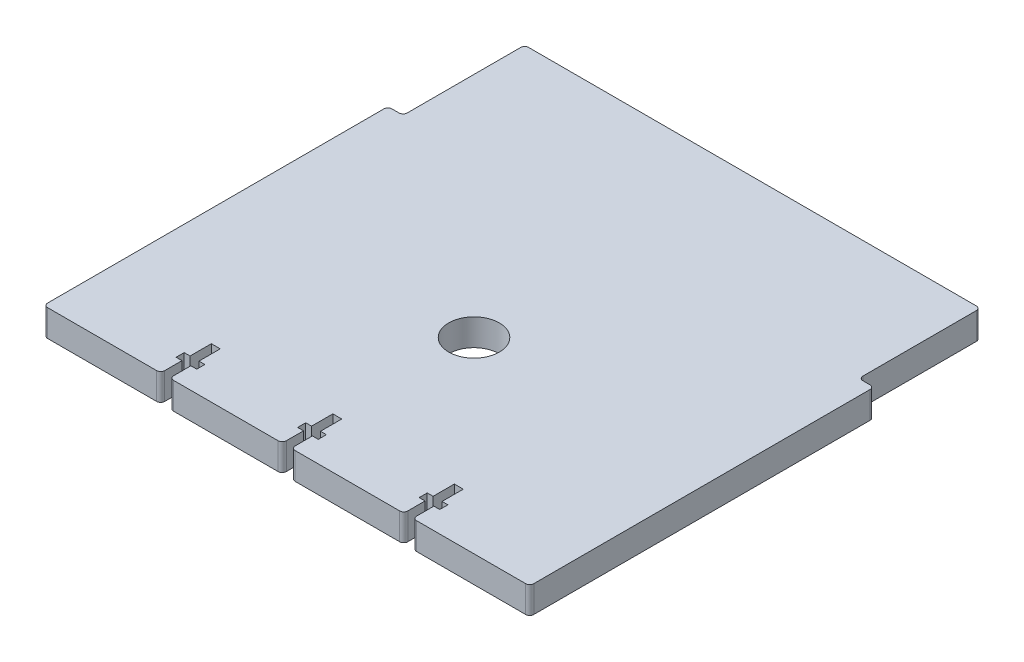
SolidWorks part; units mm, degrees
ref_plane "Front Plane" through (0, 0, 0) normal (0, 0, 1) x (1, 0, 0)
ref_plane "Top Plane" through (0, 0, 0) normal (0, 1, 0) x (1, 0, 0)
ref_plane "Right Plane" through (0, 0, 0) normal (1, 0, 0) x (0, 0, -1)
sketch "Sketch1" plane through (0, 0, 0) normal (0, 1, 0) x (1, 0, 0)
  line L1 (0, 0) -> (142.875, 0)
  line L2 (0, 107.95) -> (0, 146.05)
  line L3 (0, 146.05) -> (142.875, 146.05)
  line L4 (142.875, 107.95) -> (142.875, 146.05)
  line L5 (142.875, 0) -> (147.6375, 0)
  line L7 (142.875, 107.95) -> (147.6375, 107.95)
  line L8 (147.6375, 0) -> (147.6375, 107.95)
  line L9 (0, 0) -> (-4.7625, 0)
  line L11 (0, 107.95) -> (-4.7625, 107.95)
  line L12 (-4.7625, 0) -> (-4.7625, 107.95)
  dimension "D1" = 142.875
  dimension "D2" = 146.05
  dimension "D3" = 4.7625
  dimension "D4" = 4.7625
  dimension "D5" = 107.95
  dimension "D6" = 107.95
extrude "Boss-Extrude1" add sketch "Sketch1" along normal blind 8.382
sketch "Sketch10" plane through (0, 8.382, 0) normal (0, 1, 0) x (1, 0, 0)
  line L0 (71.4375, 146.05) -> (71.4375, 15.875) construction
  line L1 (70.0405, 9.2075) -> (68.199, 9.2075)
  line L2 (108.1405, 15.875) -> (110.9345, 15.875)
  line L3 (142.875, 146.05) -> (0, 146.05) construction
  line L4 (-4.7625, 0) -> (147.6375, 0) construction
  line L5 (70.0405, 6.6675) -> (70.0405, 0)
  line L6 (70.0405, 15.875) -> (72.8345, 15.875)
  line L7 (70.0405, 15.875) -> (70.0405, 9.2075)
  line L8 (70.0405, 0) -> (72.8345, 0)
  line L9 (72.8345, 15.875) -> (72.8345, 9.2075)
  line L10 (108.1405, 15.875) -> (108.1405, 9.2075)
  line L11 (110.9345, 15.875) -> (110.9345, 9.2075)
  line L12 (74.676, 6.6675) -> (72.8345, 6.6675)
  line L13 (74.676, 6.6675) -> (74.676, 9.2075)
  line L14 (74.676, 9.2075) -> (72.8345, 9.2075)
  line L15 (68.199, 6.6675) -> (68.199, 9.2075)
  line L16 (112.776, 9.2075) -> (110.9345, 9.2075)
  line L17 (112.776, 6.6675) -> (112.776, 9.2075)
  line L18 (70.0405, 6.6675) -> (68.199, 6.6675)
  line L19 (112.776, 6.6675) -> (110.9345, 6.6675)
  line L20 (110.9345, 6.6675) -> (110.9345, 0)
  line L21 (108.1405, 0) -> (110.9345, 0)
  line L22 (108.1405, 6.6675) -> (108.1405, 0)
  line L23 (108.1405, 6.6675) -> (106.299, 6.6675)
  line L24 (106.299, 6.6675) -> (106.299, 9.2075)
  line L25 (108.1405, 9.2075) -> (106.299, 9.2075)
  line L26 (72.8345, 6.6675) -> (72.8345, 0)
  line L27 (34.7345, 15.875) -> (34.7345, 9.2075)
  line L28 (31.9405, 15.875) -> (34.7345, 15.875)
  line L29 (31.9405, 15.875) -> (31.9405, 9.2075)
  line L30 (31.9405, 9.2075) -> (30.099, 9.2075)
  line L31 (30.099, 6.6675) -> (30.099, 9.2075)
  line L32 (31.9405, 6.6675) -> (30.099, 6.6675)
  line L33 (31.9405, 6.6675) -> (31.9405, 0)
  line L34 (34.7345, 6.6675) -> (34.7345, 0)
  line L35 (31.9405, 0) -> (34.7345, 0)
  line L36 (36.576, 6.6675) -> (34.7345, 6.6675)
  line L37 (36.576, 6.6675) -> (36.576, 9.2075)
  line L38 (36.576, 9.2075) -> (34.7345, 9.2075)
  point P6 (71.4375, 7.9375)
  point P11 (71.4375, 7.9375)
  dimension "D1" = 2.794
  dimension "D2" = 15.875
  dimension "D3" = 2.54
  dimension "D4" = 6.477
  dimension "D5" = 2
  dimension "D6" = 2
extrude "Cut-Extrude2" cut sketch "Sketch10" against normal through all
hole_wizard "5/8 (0.625) Diameter Hole1" positions "Sketch11" profile "Sketch13" hole size "5/8" standard "ANSI Inch" end condition through all
sketch "Sketch11" plane through (0, 0, 0) normal (0, -1, 0) x (-1, 0, 0)
  line L6 (0.127, 130.175) -> (-142.875, -12.7) construction
  point P26 (-71.4375, 58.7375)
sketch "Sketch13" plane through (71.4375, 0, -58.7375) normal (1, 0, 0) x (0, 0, -1)
  line L0 (0, 0) -> (0, 8.382)
  line L1 (0, 8.382) -> (7.9375, 8.382)
  line L2 (7.9375, 8.382) -> (7.9375, 0)
  line L5 (7.9375, 0) -> (0, 0)
  line L11 (0, -6.35) -> (0, 107.95) construction
  dimension "Thru Hole Dia." = 15.875
  dimension "Thru Hole Depth" = 8.382
fillet "Fillet1" radius 1.27 14 edges at (72.8345, 4.191, 0) (70.0405, 4.191, 0) (147.6375, 4.191, -107.95) (142.875, 4.191, -107.95) (142.875, 4.191, -146.05) (0, 4.191, -107.95) (0, 4.191, -146.05) (-4.7625, 4.191, -107.95) (-4.7625, 4.191, 0) (147.6375, 4.191, 0) (108.1405, 4.191, 0) (110.9345, 4.191, 0) (34.7345, 4.191, 0) (31.9405, 4.191, 0)
